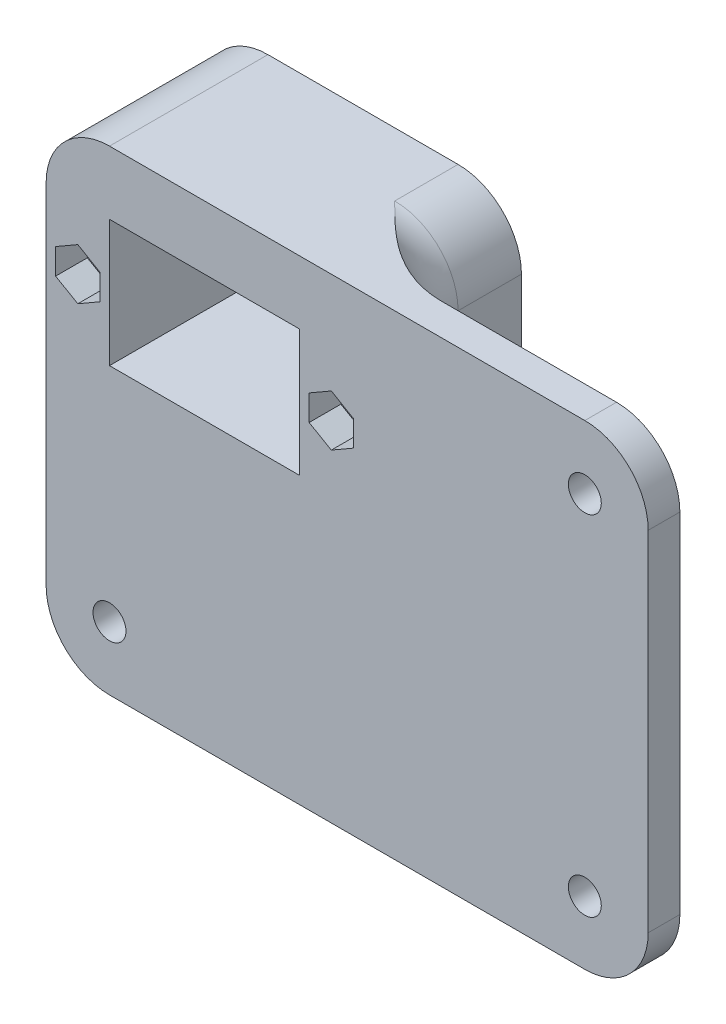
SolidWorks part; units mm, degrees
ref_plane "前视基准面" through (0, 0, 0) normal (0, 0, 1) x (1, 0, 0)
ref_plane "上视基准面" through (0, 0, 0) normal (0, 1, 0) x (1, 0, 0)
ref_plane "右视基准面" through (0, 0, 0) normal (1, 0, 0) x (0, 0, -1)
sketch "草图1" plane through (0, 0, 0) normal (0, 0, 1) x (1, 0, 0)
  line L1 (-15, -10) -> (15, -10)
  line L2 (-15, -10) -> (-15, 10)
  line L3 (-15, 10) -> (15, 10)
  line L4 (15, -10) -> (15, 10)
  line L5 (-15, -10) -> (15, 10) construction
  line L6 (-15, 10) -> (15, -10) construction
  line L7 (-25, 20) -> (70, 20)
  line L8 (-25, 20) -> (-25, -55)
  line L9 (-25, -55) -> (70, -55)
  line L10 (70, 20) -> (70, -55)
  point P0 (0, 0)
  dimension "D1" = 30
  dimension "D2" = 20
  dimension "D3" = 85
  dimension "D4" = 65
  dimension "D5" = 10
  dimension "D6" = 10
extrude "凸台-拉伸1" add sketch "草图1" along normal blind 5
sketch "草图2" plane through (0, 0, 5) normal (0, 0, 1) x (1, 0, 0)
  line L1 (-25, 20) -> (25, 20)
  line L2 (-25, 20) -> (-25, -20)
  line L3 (-25, -20) -> (25, -20)
  line L4 (25, 20) -> (25, -20)
  line L5 (-15, 10) -> (15, 10)
  line L6 (-15, 10) -> (-15, -10)
  line L7 (-15, -10) -> (15, -10)
  line L8 (15, 10) -> (15, -10)
  dimension "D1" = 10
  dimension "D2" = 10
extrude "凸台-拉伸2" add sketch "草图2" against normal blind 20 from surface starting at face at (22.5, -17.5, 0)
sketch "草图3" plane through (0, 0, -20) normal (0, 0, -1) x (-1, 0, 0)
  line L0 (-20, 0) -> (20, 0) construction
  circle A0 centre (20, 0) radius 2.2
  circle A1 centre (-20, 0) radius 2.2
  point P4 (0, 0)
  dimension "D2" = 4.4
  dimension "D1" = 40
extrude "切除-拉伸1" cut sketch "草图3" against normal through all both and the other way through all
sketch "草图4" plane through (0, 0, 0) normal (0, 0, -1) x (-1, 0, 0)
  line L1 (20, 4.0415) -> (16.5, 2.0207)
  line L2 (16.5, 2.0207) -> (16.5, -2.0207)
  line L3 (16.5, -2.0207) -> (20, -4.0415)
  line L4 (20, -4.0415) -> (23.5, -2.0207)
  line L5 (23.5, -2.0207) -> (23.5, 2.0207)
  line L6 (23.5, 2.0207) -> (20, 4.0415)
  line L7 (-20, 4.0415) -> (-23.5, 2.0207)
  line L8 (-23.5, 2.0207) -> (-23.5, -2.0207)
  line L9 (-23.5, -2.0207) -> (-20, -4.0415)
  line L10 (-20, -4.0415) -> (-16.5, -2.0207)
  line L11 (-16.5, -2.0207) -> (-16.5, 2.0207)
  line L12 (-16.5, 2.0207) -> (-20, 4.0415)
  circle A0 centre (20, 0) radius 3.5 construction
  circle A1 centre (-20, 0) radius 3.5 construction
  dimension "D1" = 7
extrude "切除-拉伸2" cut sketch "草图4" against normal blind 5
sketch "草图5" plane through (0, 0, 5) normal (0, 0, 1) x (1, 0, 0)
  line L3 (-25, 20) -> (-25, -55) construction
  line L5 (-25, -45) -> (60, -45)
  line L6 (60, -45) -> (60, 20)
  line L7 (-25, -45) -> (60, -45) construction
  line L8 (60, -45) -> (60, 20) construction
  circle A0 centre (60, -45) radius 2.6
  circle A1 centre (-15, -45) radius 2.6
  circle A2 centre (60, 10) radius 2.6
  dimension "D2" = 5.2
  dimension "D3" = 10
  dimension "D4" = 10
  dimension "D1" = 10
extrude "切除-拉伸3" cut sketch "草图5" against normal through all
fillet "圆角4" radius 10 7 edges at (70, -55, 2.5) (-25, -55, 2.5) (-25, -20, -10) (25, -20, -10) (70, 20, 2.5) (-25, 20, -7.5) (25, 20, -10)
fillet "圆角5" radius 10 5 edges at (-22.0711, -17.0711, 0) (0, -20, 0) (22.0711, -17.0711, 0) (22.0711, 17.0711, 0) (25, 0, 0)
